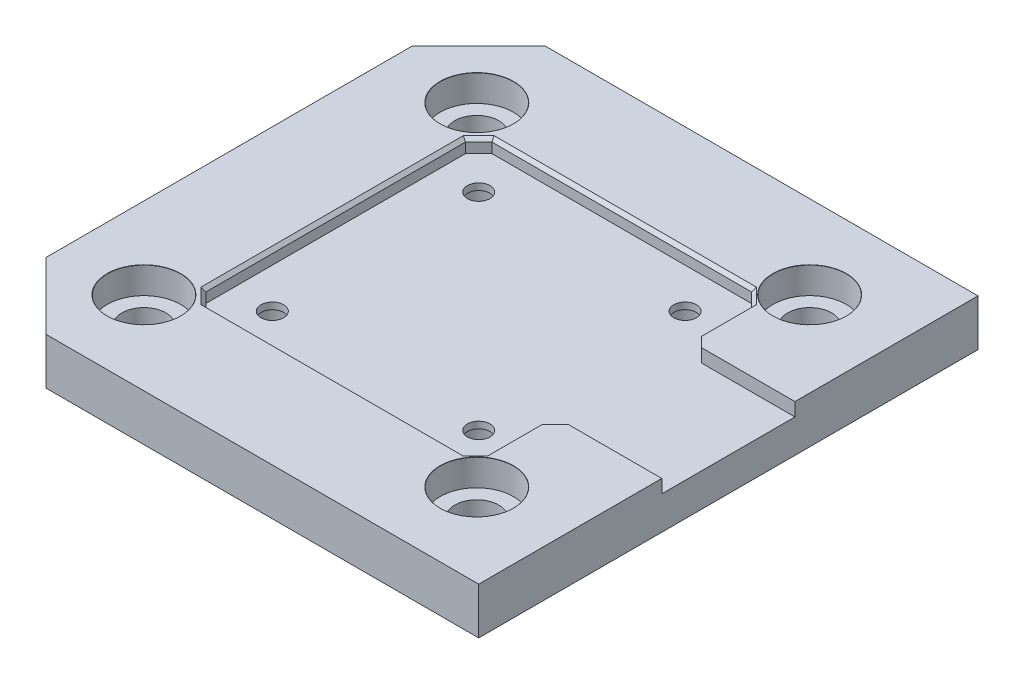
SolidWorks part; units mm, degrees
ref_plane "Front Plane" through (0, 0, 0) normal (0, 0, 1) x (1, 0, 0)
ref_plane "Top Plane" through (0, 0, 0) normal (0, 1, 0) x (1, 0, 0)
ref_plane "Right Plane" through (0, 0, 0) normal (1, 0, 0) x (0, 0, -1)
sketch "Sketch1" plane through (0, 0, 0) normal (0, 1, 0) x (1, 0, 0)
  line L0 (0, 37.5) -> (-37.5, 37.5)
  line L1 (-37.5, 37.5) -> (-37.5, -37.5)
  line L2 (-37.5, -37.5) -> (0, -37.5)
  line L3 (0, -37.5) -> (37.5, -37.5)
  line L4 (37.5, -37.5) -> (37.5, 37.5)
  line L5 (37.5, 37.5) -> (0, 37.5)
  line L6 (-37.5, 37.5) -> (37.5, -37.5) construction
  line L7 (37.5, 37.5) -> (-37.5, -37.5) construction
  point P2 (0, 0)
  dimension "D1" = 75
  dimension "D2" = 37.5
  dimension "D3" = 37.5
extrude "Boss-Extrude1" add sketch "Sketch1" along normal blind 7
sketch "Sketch2" plane through (0, 7, 0) normal (0, -1, 0) x (1, 0, 0)
  line L1 (-25.29, 25) -> (49.71, 25) construction
  line L2 (-25.29, 25) -> (-25.29, -25) construction
  line L3 (-25.29, -25) -> (49.71, -25) construction
  line L4 (49.71, 25) -> (49.71, -25) construction
  line L5 (-25.29, 25) -> (49.71, -25) construction
  line L6 (-25.29, -25) -> (49.71, 25) construction
  point P0 (24.71, -25)
  point P1 (49.71, -25)
  point P2 (12.21, 0)
  point P3 (49.71, 25)
  point P4 (24.71, 25)
  point P10 (-25.29, -25)
  point P11 (-25.29, 25)
  dimension "D1" = 49.71
  dimension "D2" = 25
  dimension "D5" = 25
  dimension "D3" = 75
  dimension "D4" = 50
hole_wizard "Hole3" positions "Sketch13" profile "Sketch14" legacy end condition through all
sketch "Sketch13" plane through (0, 7, 0) normal (0, 1, 0) x (1, 0, 0)
  point P15 (-25.29, -25)
  point P18 (-25.29, 25)
  point P21 (24.71, 25)
  point P24 (24.71, -25)
sketch "Sketch14" plane through (-25.29, 7, 25) normal (1, 0, 0) x (0, 0, 1)
  line L0 (0, 0) -> (0, 7)
  line L1 (3.3, 6.975) -> (3.325, 7)
  line L2 (5.5, 4) -> (3.3, 4)
  line L3 (3.3, 4) -> (3.3, 6.975)
  line L5 (5.5, 4) -> (5.5, 0.025)
  line L6 (5.5, 0.025) -> (5.525, 0)
  line L7 (5.525, 0) -> (0, 0)
  line L8 (-5.5, 0.025) -> (-5.525, 0) construction
  line L11 (0, -6.35) -> (0, 107.95) construction
  line L12 (3.325, 7) -> (0, 7)
  line L13 (-3.3, 6.975) -> (-3.325, 7) construction
  dimension "Thru Hole Dia." = 6.6
  dimension "Thru Hole Depth" = 7
  dimension "C'Bore Dia." = 11
  dimension "C'Bore Depth" = 4
  dimension "Near C'Sink Dia." = 11.05
  dimension "Near C'Sink Angle" = 90
  dimension "Far C'Sink Dia." = 6.65
  dimension "Far C'Sink Angle" = 90
sketch "Sketch9" plane through (0, 7, 0) normal (0, 1, 0) x (1, 0, 0)
  line L0 (21.5, 19.5) -> (19.5, 21.5)
  line L1 (-19.5, 21.5) -> (19.5, 21.5)
  line L2 (-21.5, 19.5) -> (-21.5, -19.5)
  line L3 (-19.5, -21.5) -> (19.5, -21.5)
  line L4 (21.5, 19.5) -> (21.5, 12)
  line L5 (-20.5, 20.5) -> (20.5, -20.5) construction
  line L6 (-20.5, -20.5) -> (20.5, 20.5) construction
  line L7 (19.5, -21.5) -> (21.5, -19.5)
  line L8 (-21.5, -19.5) -> (-19.5, -21.5)
  line L9 (-19.5, 21.5) -> (-21.5, 19.5)
  line L10 (23.5, 10) -> (37.5, 10)
  line L11 (37.5, -37.5) -> (37.5, 37.5) construction
  line L12 (37.5, 10) -> (37.5, 0)
  line L13 (37.5, -10) -> (23.5, -10)
  line L14 (21.5, 0) -> (37.5, 0) construction
  line L15 (37.5, 0) -> (37.5, -10)
  line L16 (37.5, -10) -> (37.3058, -10.0345)
  line L17 (21.5, -12) -> (21.5, -19.5)
  line L18 (21.5, 12) -> (23.5, 10)
  line L19 (23.5, -10) -> (21.5, -12)
  point P0 (0, 0)
  point P2 (21.5, 10)
  point P17 (0, 0)
  point P20 (21.5, -10)
  dimension "D1" = 4
  dimension "D2" = 10
  dimension "D4" = 2
extrude "Cut-Extrude3" cut sketch "Sketch9" against normal blind 2 contours L13 L19 L17 L7 L3 L8 L2 L9 L1 L0 L4 L18 L10 L12 L15
sketch "Sketch10" plane through (0, 0, 0) normal (0, 1, 0) x (1, 0, 0)
  line L1 (15.5, 15.5) -> (-15.5, 15.5) construction
  line L2 (15.5, 15.5) -> (15.5, -15.5) construction
  line L3 (15.5, -15.5) -> (-15.5, -15.5) construction
  line L4 (-15.5, 15.5) -> (-15.5, -15.5) construction
  line L5 (15.5, 15.5) -> (-15.5, -15.5) construction
  line L6 (15.5, -15.5) -> (-15.5, 15.5) construction
  point P0 (0, 0)
  point P7 (-15.5, -15.5)
  point P8 (-15.5, 15.5)
  point P9 (15.5, 15.5)
  point P10 (15.5, -15.5)
  dimension "D1" = 31
  dimension "D2" = 31
hole_wizard "Hole2" positions "Sketch11" profile "Sketch12" legacy end condition through all
sketch "Sketch11" plane through (0, 0, 0) normal (0, -1, 0) x (-1, 0, 0)
  point P0 (15.5, 15.5)
  point P3 (-15.5, 15.5)
  point P6 (-15.5, -15.5)
  point P9 (15.5, -15.5)
sketch "Sketch12" plane through (-15.5, 0, -15.5) normal (1, 0, 0) x (0, 0, -1)
  line L0 (0, 0) -> (0, 7)
  line L1 (1.7, 6.975) -> (1.725, 7)
  line L2 (3.25, 4) -> (1.7, 4)
  line L3 (1.7, 4) -> (1.7, 6.975)
  line L5 (3.25, 4) -> (3.25, 0.025)
  line L6 (3.25, 0.025) -> (3.275, 0)
  line L7 (3.275, 0) -> (0, 0)
  line L8 (-3.25, 0.025) -> (-3.275, 0) construction
  line L11 (0, -6.35) -> (0, 107.95) construction
  line L12 (1.725, 7) -> (0, 7)
  line L13 (-1.7, 6.975) -> (-1.725, 7) construction
  dimension "Thru Hole Dia." = 3.4
  dimension "Thru Hole Depth" = 7
  dimension "C'Bore Dia." = 6.5
  dimension "C'Bore Depth" = 4
  dimension "Near C'Sink Dia." = 6.55
  dimension "Near C'Sink Angle" = 90
  dimension "Far C'Sink Dia." = 3.45
  dimension "Far C'Sink Angle" = 90
chamfer "Chamfer1" distance 0.5 angle 45 8 edges at (20.5, 7, 20.5) (21.5, 7, -15.75) (20.5, 7, -20.5) (0, 7, 21.5) (-20.5, 7, 20.5) (-21.5, 7, 0) (-20.5, 7, -20.5) (0, 7, -21.5)
chamfer "Chamfer2" distance 10 angle 45 2 edges at (-37.5, 3.5, 37.5) (-37.5, 3.5, -37.5)
